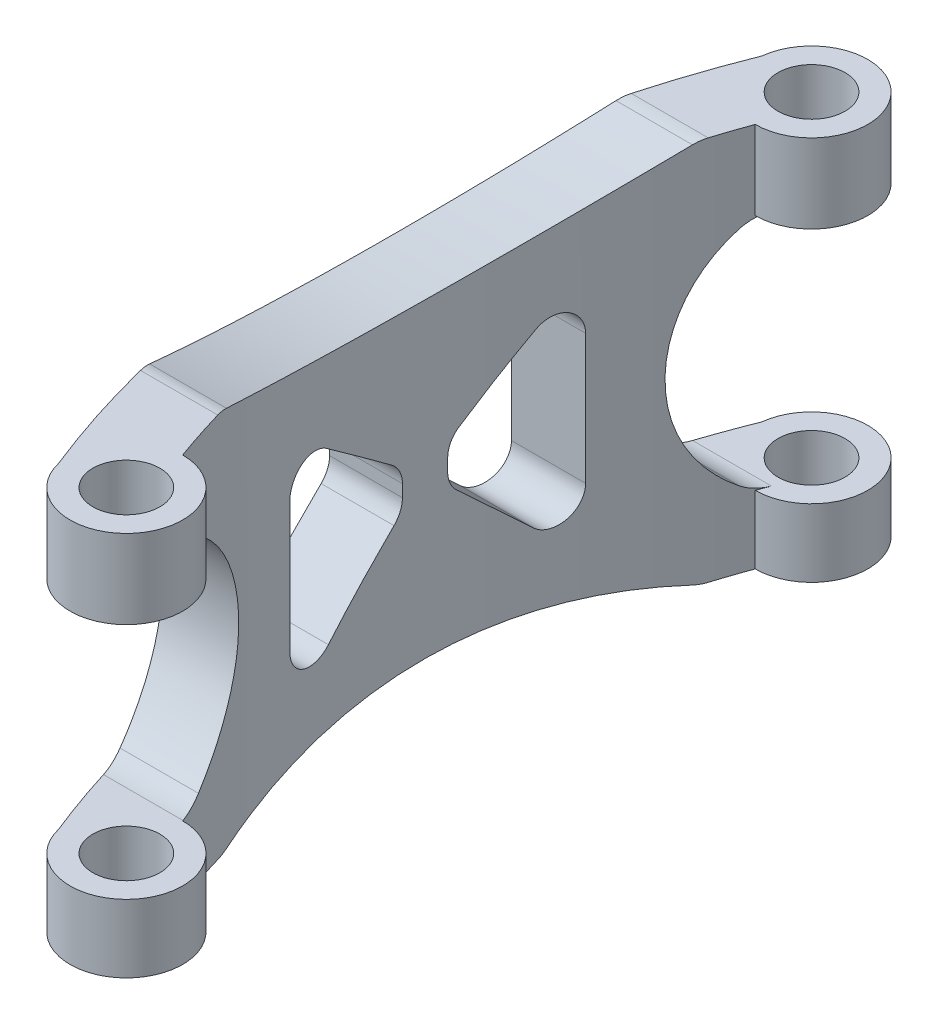
SolidWorks part; units mm, degrees
material "Default"
ref_plane "Top" through (0, 0, 0) normal (0, 0, 1) x (1, 0, 0)
ref_plane "Right" through (0, 0, 0) normal (0, 1, 0) x (1, 0, 0)
ref_plane "Front" through (0, 0, 0) normal (1, 0, 0) x (0, 0, -1)
sketch "Sketch1" plane through (0, -77.0797, 0) normal (0, 1, 0) x (1, 0, 0)
  arc A0 (6.6296, 141.6706) -> (1.3306, 147.6145) centre (6.6296, 147.0046) ccw
  circle A1 centre (6.6296, 147.0046) radius 3.175
  arc A2 (1.4394, 80.8744) -> (6.6296, 87.4388) centre (6.6296, 82.1048) ccw
  circle A3 centre (6.6296, 82.1048) radius 3.175
  circle A4 centre (6.6296, 82.1048) radius 2.54 construction
  arc A5 (6.6296, 87.4388) -> (6.6296, 141.6706) centre (81.2753, 114.5547) cw
  arc A6 (1.4394, 80.8744) -> (1.3306, 147.6145) centre (84.8616, 114.3806) cw
  point P5 (0, 0)
  dimension "D1" = 10.668
  dimension "D2" = 6.35
extrude "Boss-Extrude1" add sketch "Sketch1" along normal up to surface (36.4658 mm away)
sketch "Sketch2" plane through (14.9897, 0, 0) normal (-1, 0, 0) x (0, 0, 1)
  line L0 (-147.6145, -40.6301) -> (-76.7708, -40.6301) construction
  line L1 (-141.6706, -40.6301) -> (-141.6706, -48.0962) construction
  line L2 (-87.4388, -40.6301) -> (-87.4388, -43.6218) construction
  line L4 (-141.6706, -48.0962) -> (-158.2792, -48.0962)
  line L5 (-158.2792, -48.0962) -> (-158.2792, -70.6311)
  line L6 (-158.2792, -70.6311) -> (-141.6706, -70.6311)
  line L7 (-115.1386, -40.6301) -> (-115.1386, -58.4369) construction
  line L8 (-88.6065, -48.0962) -> (-71.9979, -48.0962)
  line L9 (-71.9979, -48.0962) -> (-71.9979, -70.6311)
  line L10 (-71.9979, -70.6311) -> (-88.6065, -70.6311)
  line L11 (-129.0448, -48.0962) -> (-129.0448, -71.2567)
  line L12 (-129.0448, -71.2567) -> (-117.2664, -60.3985)
  line L13 (-117.2664, -56.8547) -> (-129.0448, -48.0962)
  line L14 (-101.2324, -71.2567) -> (-113.0107, -60.3985)
  line L15 (-101.2324, -48.0962) -> (-101.2324, -71.2567)
  line L16 (-113.0107, -56.8547) -> (-101.2324, -48.0962)
  line L17 (-117.2664, -56.8547) -> (-117.2664, -60.3985)
  line L18 (-113.0107, -56.8547) -> (-113.0107, -60.3985)
  line L19 (-147.6145, -77.0797) -> (-80.8744, -77.0797) construction
  line L20 (-137.7531, -77.0797) -> (-137.7531, -80.7243)
  line L21 (-137.7531, -80.7243) -> (-92.9717, -80.7243)
  line L22 (-92.9717, -80.7243) -> (-92.9717, -77.0797)
  line L23 (-152.3386, -40.6138) -> (-152.3386, -77.0797) construction
  line L24 (-152.3386, -58.8467) -> (-98.6899, -58.8467) construction
  line L25 (-92.9717, -36.9692) -> (-92.9717, -40.6138)
  line L26 (-137.7531, -36.9692) -> (-92.9717, -36.9692)
  line L27 (-137.7531, -40.6138) -> (-137.7531, -36.9692)
  arc A0 (-141.6706, -48.0962) -> (-141.6706, -70.6311) centre (-148.1954, -59.3636) cw
  arc A1 (-88.6065, -48.0962) -> (-88.6065, -70.6311) centre (-82.0818, -59.3636) ccw
  arc A2 (-137.7531, -77.0797) -> (-92.9717, -77.0797) centre (-115.3624, -146.4869) cw
  arc A3 (-137.7531, -40.6138) -> (-92.9717, -40.6138) centre (-115.3624, 28.7934) ccw
  dimension "D1" = 26.532
extrude "Cut-Extrude4" cut sketch "Sketch2" along normal blind 38.1
fillet "Fillet1" radius 2.54 8 edges at (-0.3219, -71.2567, -129.0448) (-0.3219, -48.0962, -129.0448) (-1.5441, -60.3985, -117.2664) (-1.5441, -56.8547, -117.2664) (-1.5777, -60.3985, -113.0107) (-1.5777, -56.8547, -113.0107) (-0.5444, -71.2567, -101.2324) (-0.5444, -48.0962, -101.2324)
fillet "Fillet2" radius 3.81 8 edges at (2.9169, -48.0962, -141.6706) (2.9169, -70.6311, -141.6706) (2.4758, -70.6311, -88.6065) (2.4758, -48.0962, -88.6065) (1.1973, -77.0797, -92.9717) (1.6871, -77.0797, -137.7531) (1.6871, -40.6138, -137.7531) (1.1973, -40.6138, -92.9717)
